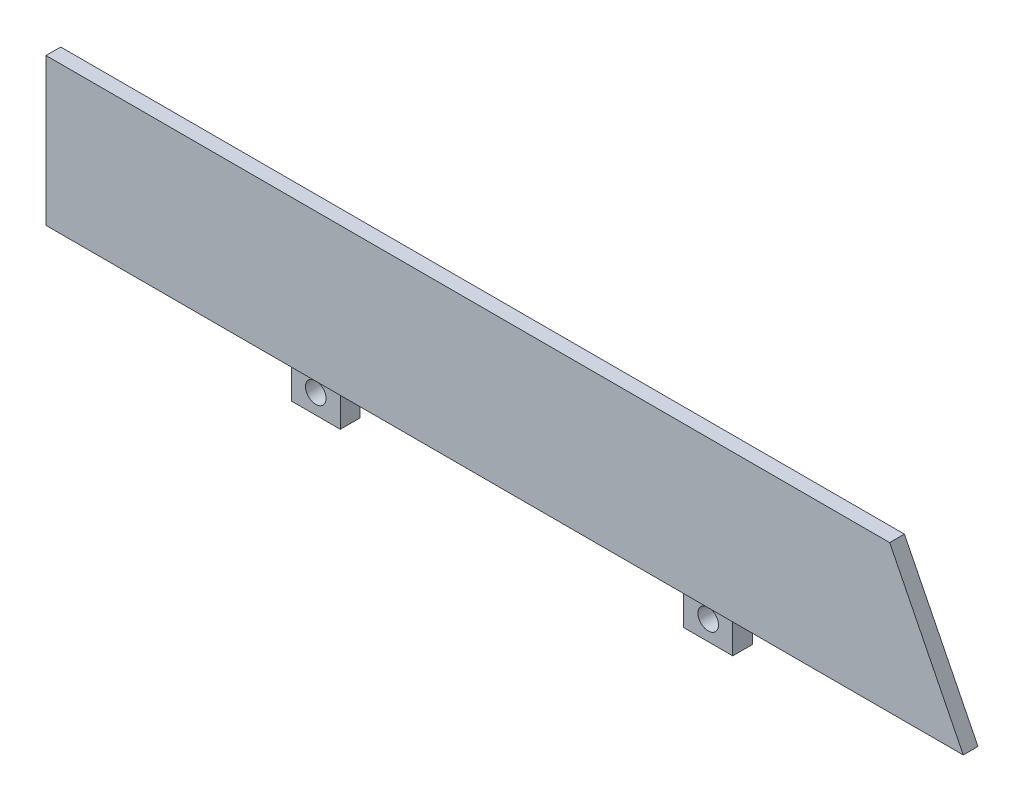
SolidWorks part; units mm, degrees
material "ABS"
ref_plane "Płaszczyzna przednia" through (0, 0, 0) normal (0, 0, 1) x (1, 0, 0)
ref_plane "Płaszczyzna górna" through (0, 0, 0) normal (0, 1, 0) x (1, 0, 0)
ref_plane "Płaszczyzna prawa" through (0, 0, 0) normal (1, 0, 0) x (0, 0, -1)
sketch "Szkic1" plane through (0, 0, 0) normal (0, 0, 1) x (1, 0, 0)
  line L0 (0, 0) -> (187, 0)
  line L1 (0, 0) -> (0, 30)
  line L2 (0, 30) -> (171.9968, 30)
  line L3 (171.9968, 30) -> (187, 0)
  dimension "D1" = 187
  dimension "D2" = 30
  dimension "D3" = 63.43
extrude "Dodanie-wyciągnięcie1" add sketch "Szkic1" along normal blind 3
sketch "Szkic2" plane through (0, 0, 0) normal (0, 0, -1) x (-1, 0, 0)
  line L0 (0, 0) -> (-187, 0) construction
  line L1 (-137, 5) -> (-127, 5)
  line L2 (-137, 5) -> (-137, -9)
  line L3 (-137, -9) -> (-127, -9)
  line L4 (-127, 5) -> (-127, -9)
  line L9 (-57, 5) -> (-47, 5)
  line L10 (-57, 5) -> (-57, -9)
  line L11 (-57, -9) -> (-47, -9)
  line L12 (-47, 5) -> (-47, -9)
  circle A0 centre (-132, -5) radius 2.1
  circle A2 centre (-52, -5) radius 2.1
  dimension "D5" = 4.2
  dimension "D7" = 5
  dimension "D1" = 10
  dimension "D2" = 14
  dimension "D3" = 5
  dimension "D4" = 50
  dimension "D6" = 4
  dimension "D8" = 2
extrude "Dodanie-wyciągnięcie2" add sketch "Szkic2" along normal blind 4
chamfer "Sfazowanie1" distance 4 angle 45 6 edges at (57, 2.5, 0) (52, 5, 0) (47, 2.5, 0) (127, 2.5, 0) (132, 5, 0) (137, 2.5, 0)
